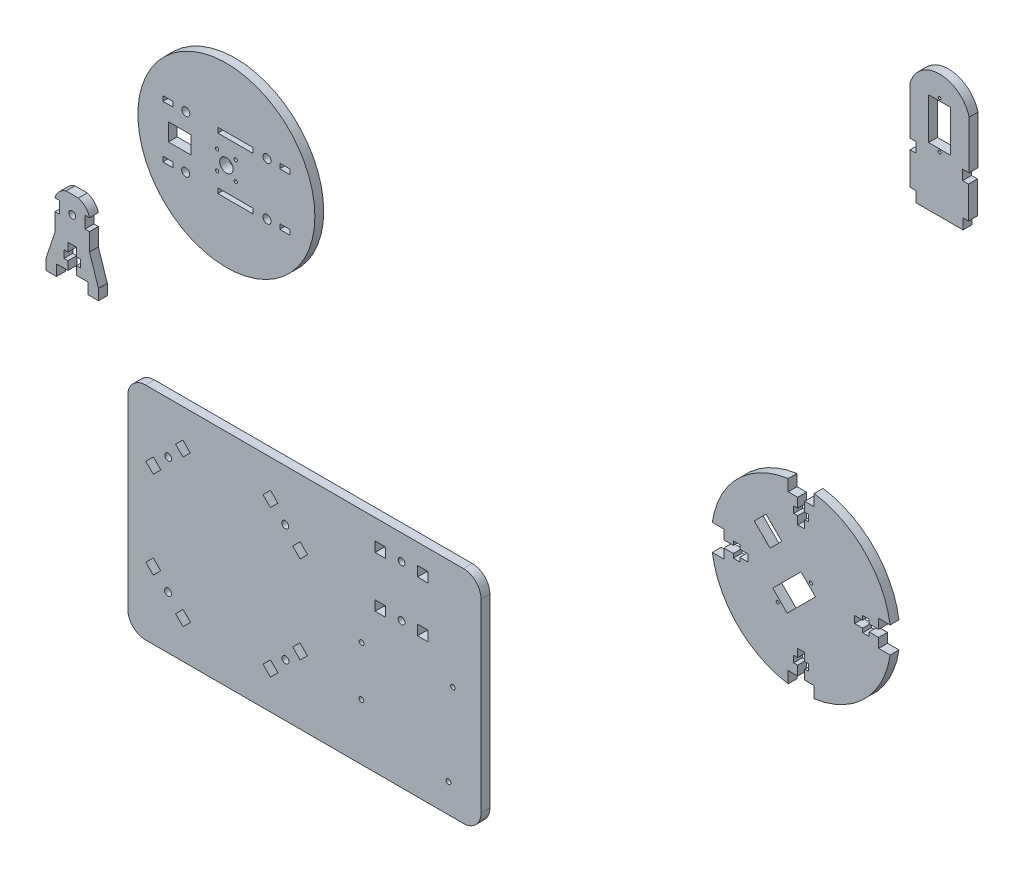
SolidWorks part; units mm, degrees
note: The reader was unsure of these and kept them because the rebuilt part matched: shared geometry of "Sketch2<4>", "Sketch3<3>", "Sketch3<4>".
ref_plane "Front Plane" through (0, 0, 0) normal (0, 0, 1) x (1, 0, 0)
ref_plane "Top Plane" through (0, 0, 0) normal (0, 1, 0) x (1, 0, 0)
ref_plane "Right Plane" through (0, 0, 0) normal (1, 0, 0) x (0, 0, -1)
sketch "Sketch2" plane through (0, 0, 0) normal (0, 0, 1) x (1, 0, 0)
  line L28 (-46.2053, 0) -> (-46.2053, 6.069)
  line L29 (199.603, -121.4578) -> (199.603, -37.9314)
  line L30 (10.2003, -65.1714) -> (14.4333, -69.3774)
  line L31 (189.603, -27.9314) -> (10, -27.9314)
  line L32 (199.603, -37.9314) -> (199.603, -142.6594)
  line L33 (189.603, -152.6594) -> (10, -152.6594)
  line L34 (0, -37.9314) -> (0, -142.6594)
  line L35 (10.2003, -65.1714) -> (14.4337, -60.9108)
  line L36 (14.4333, -69.3774) -> (18.6667, -65.1168)
  line L37 (14.4337, -60.9108) -> (18.6667, -65.1168)
  line L38 (27.0203, -48.3784) -> (31.2263, -52.6114)
  line L39 (27.0203, -48.3784) -> (31.1246, -44.3003)
  line L40 (31.2263, -52.6114) -> (35.3306, -48.5333)
  line L41 (31.1246, -44.3003) -> (35.3306, -48.5333)
  line L42 (76.3823, -48.3784) -> (80.6153, -52.6114)
  line L43 (76.3823, -48.3784) -> (80.6232, -44.1374)
  line L44 (80.6153, -52.6114) -> (84.8562, -48.3704)
  line L45 (80.6232, -44.1374) -> (84.8562, -48.3704)
  line L46 (93.1733, -65.1714) -> (97.4063, -69.3774)
  line L47 (93.1733, -65.1714) -> (97.3783, -60.9393)
  line L48 (97.4063, -69.3774) -> (101.6113, -65.1453)
  line L49 (97.3783, -60.9393) -> (101.6113, -65.1453)
  line L50 (163.7283, -44.9924) -> (169.6553, -44.9924)
  line L51 (163.7283, -44.9924) -> (163.7283, -39.3468)
  line L52 (169.6553, -44.9924) -> (169.6553, -39.3468)
  line L53 (163.7283, -39.3468) -> (169.6553, -39.3468)
  line L54 (139.7403, -44.9924) -> (145.6673, -44.9924)
  line L55 (139.7403, -44.9924) -> (139.7403, -39.3781)
  line L56 (145.6673, -44.9924) -> (145.6673, -39.3781)
  line L57 (139.7403, -39.3781) -> (145.6673, -39.3781)
  line L58 (163.7283, -73.7784) -> (169.6553, -73.7784)
  line L59 (163.7283, -73.7784) -> (163.7283, -68.0524)
  line L60 (169.6553, -73.7784) -> (169.6553, -68.0524)
  line L61 (163.7283, -68.0524) -> (169.6553, -68.0524)
  line L62 (139.7403, -73.7784) -> (145.6673, -73.7784)
  line L63 (139.7403, -73.7784) -> (139.7403, -68.1856)
  line L64 (145.6673, -73.7784) -> (145.6673, -68.1856)
  line L65 (139.7403, -68.1856) -> (145.6673, -68.1856)
  line L66 (10.2003, -114.5602) -> (14.4333, -118.7663)
  line L67 (10.2003, -114.5602) -> (14.406, -110.3275)
  line L68 (14.4333, -118.7663) -> (18.639, -114.5336)
  line L69 (14.406, -110.3275) -> (18.639, -114.5336)
  line L70 (26.9933, -131.3532) -> (31.2263, -135.5866)
  line L71 (26.9933, -131.3532) -> (31.2249, -127.122)
  line L72 (31.2263, -135.5866) -> (35.4579, -131.3554)
  line L73 (31.2249, -127.122) -> (35.4579, -131.3554)
  line L74 (76.3823, -131.3532) -> (80.6153, -135.5866)
  line L75 (76.3823, -131.3532) -> (80.6148, -127.1211)
  line L76 (80.6153, -135.5866) -> (84.8478, -131.3545)
  line L77 (80.6148, -127.1211) -> (84.8478, -131.3545)
  line L78 (93.1733, -114.5602) -> (97.4063, -118.7936)
  line L79 (93.1733, -114.5602) -> (97.2631, -110.4707)
  line L80 (97.4063, -118.7936) -> (101.4961, -114.7041)
  line L81 (97.2631, -110.4707) -> (101.4961, -114.7041)
  line L82 (-46.2053, 6.069) -> (-41.1253, 21.309)
  line L83 (-41.1253, 21.309) -> (-41.1253, 31.309)
  line L84 (-41.1253, 31.309) -> (-38.5853, 31.309)
  line L85 (-38.5853, 31.309) -> (-38.5853, 38.082)
  line L86 (-38.5853, 38.082) -> (-41.1253, 38.082)
  line L87 (-46.2053, 0) -> (-40.2783, 0)
  line L88 (-40.2783, 0) -> (-40.2783, 6.209)
  line L89 (-40.2783, 6.209) -> (-33.7883, 6.209)
  line L90 (-33.7883, 6.209) -> (-33.7883, 11.008)
  line L91 (-33.7883, 11.008) -> (-36.0453, 11.008)
  line L92 (-36.0453, 11.008) -> (-36.0453, 15.241)
  line L93 (-36.0453, 15.241) -> (-33.7873, 15.241)
  line L94 (-33.7873, 15.241) -> (-33.7873, 20.019)
  line L95 (-33.7873, 20.019) -> (-28.9633, 20.019)
  line L96 (-31.3753, 20.019) -> (-31.3753, 15.222)
  line L110 (-34.8506, 44.6171) -> (-31.3662, 44.6171)
  line L111 (-31.3753, 34.659) -> (-31.3753, -6.6875) construction
  line L112 (0, 0) -> (-40.2783, 0) construction
  line L113 (-16.5453, 0) -> (-22.4723, 0)
  line L114 (-27.9001, 44.6171) -> (-31.3845, 44.6171)
  line L115 (-28.9633, 15.241) -> (-28.9633, 20.019)
  line L116 (-26.7053, 15.241) -> (-28.9633, 15.241)
  line L117 (-26.7053, 11.008) -> (-26.7053, 15.241)
  line L118 (-28.9623, 11.008) -> (-26.7053, 11.008)
  line L119 (-28.9623, 6.209) -> (-28.9623, 11.008)
  line L120 (-22.4723, 6.209) -> (-28.9623, 6.209)
  line L121 (-22.4723, 0) -> (-22.4723, 6.209)
  line L122 (-24.1653, 38.082) -> (-21.6253, 38.082)
  line L123 (-24.1653, 31.309) -> (-24.1653, 38.082)
  line L124 (-21.6253, 31.309) -> (-24.1653, 31.309)
  line L125 (-21.6253, 21.309) -> (-21.6253, 31.309)
  line L126 (-16.5453, 6.069) -> (-21.6253, 21.309)
  line L127 (-16.5453, 0) -> (-16.5453, 6.069)
  line L128 (22.8394, -56.7305) -> (106.4635, -140.1948) construction
  line L129 (22.7571, -122.886) -> (88.9638, -56.7949) construction
  line L130 (22.7571, -122.886) -> (38.9461, -139.075) construction
  line L131 (22.7571, -122.886) -> (3.8152, -103.9442) construction
  line L132 (0, 0) -> (0, -90.2954) construction
  arc A0 (199.603, -37.9314) -> (189.603, -27.9314) centre (189.603, -37.9314) ccw
  arc A1 (189.603, -152.6594) -> (199.603, -142.6594) centre (189.603, -142.6594) ccw
  arc A2 (10, -152.6594) -> (0, -142.6594) centre (10, -142.6594) cw
  arc A3 (10, -27.9314) -> (0, -37.9314) centre (10, -37.9314) ccw
  arc A4 (199.603, -37.9314) -> (189.603, -27.9314) centre (189.603, -37.9314) ccw
  circle A5 centre (22.8394, -56.7305) radius 1.9277
  circle A6 centre (88.9638, -56.7949) radius 1.9654
  circle A7 centre (154.6946, -42.0768) radius 1.8926
  circle A8 centre (154.6904, -70.942) radius 1.9315
  circle A9 centre (132.0883, -92.915) radius 1.329
  circle A10 centre (183.6758, -88.8865) radius 1.2561
  circle A11 centre (22.7571, -122.886) radius 1.955
  circle A12 centre (89.0892, -122.8537) radius 1.9478
  circle A13 centre (132.0182, -120.8684) radius 1.3462
  circle A14 centre (181.2213, -136.408) radius 1.3886
  circle A17 centre (-31.3753, 34.659) radius 1.955
  arc A19 (-34.8506, 44.6171) -> (-41.1253, 38.082) centre (-32.2253, 35.8165) ccw
  arc A20 (-27.9001, 44.6171) -> (-21.6253, 38.082) centre (-30.5254, 35.8165) cw
  point P2 (33.3421, -133.471)
  dimension "D1" = 10
  dimension "D2" = 10
  dimension "D3" = 6.49
  dimension "D15" = 3.91
  dimension "D16" = 14.64
  dimension "D18" = 3.91
  dimension "D19" = 5.984
  dimension "D4" = 5.927
  dimension "D5" = 2.54
  dimension "D6" = 7.338
  dimension "D7" = 6.773
  dimension "D8" = 10
  dimension "D9" = 15.24
  dimension "D10" = 6.069
  dimension "D11" = 40.2783
  dimension "D12" = 5.08
  dimension "D13" = 34.659
  dimension "D14" = 9.9582
  dimension "D17" = 9.75
  dimension "D20" = 46.8819
extrude "Boss-Extrude3" add sketch "Sketch2" along normal blind 5 contours L31 A3 L34 A2 L33 A1 L32 L29 A0 A14 A13 A12 A11 A10 A9 A8 A7 A6 A5 L79 L81 L80 L78 L75 L77 L76 L74 L71 L73 L72 L70 L67 L69 L68 L66 L63
extrude "Boss-Extrude4" add sketch "Sketch2<4>" along normal blind 5 separate body
sketch "Sketch2<4>" plane through (0, 0, 0) normal (0, 0, 1) x (1, 0, 0) same geometry as "Sketch2"
sketch "Sketch3" plane through (0, 0, 5) normal (0, 0, 1) x (1, 0, 0)
  line L0 (24.835, 123.613) -> (30.4795, 123.613)
  line L1 (24.835, 123.613) -> (24.835, 120.7918)
  line L2 (30.4795, 123.613) -> (30.4795, 120.7918)
  line L3 (24.835, 120.7918) -> (30.4795, 120.7918)
  line L4 (27.9395, 102.4605) -> (40.6396, 102.4605)
  line L5 (27.9395, 102.4605) -> (27.9395, 112.3605)
  line L6 (40.6396, 102.4605) -> (40.6396, 112.3605)
  line L7 (27.9395, 112.3605) -> (40.6396, 112.3605)
  line L8 (24.835, 91.1572) -> (30.4795, 91.1572)
  line L9 (24.835, 91.1572) -> (24.835, 94.0005)
  line L10 (30.4795, 91.1572) -> (30.4795, 94.0005)
  line L11 (24.835, 94.0005) -> (30.4795, 94.0005)
  line L12 (55.8789, 91.1572) -> (55.8789, 93.9795)
  line L13 (55.8789, 91.1572) -> (75.6506, 91.1572)
  line L14 (55.8789, 93.9795) -> (75.6506, 93.9795)
  line L15 (75.6506, 91.1572) -> (75.6506, 93.9795)
  line L16 (55.8789, 120.79) -> (75.6348, 120.79)
  line L17 (55.8789, 120.79) -> (55.8789, 123.646)
  line L18 (75.6348, 120.79) -> (75.6348, 123.646)
  line L19 (55.8789, 123.646) -> (75.6348, 123.646)
  line L20 (90.876, 120.79) -> (96.5205, 120.79)
  line L21 (90.876, 120.79) -> (90.876, 123.5848)
  line L22 (96.5205, 120.79) -> (96.5205, 123.5848)
  line L23 (90.876, 123.5848) -> (96.5205, 123.5848)
  line L24 (90.876, 91.1572) -> (96.5205, 91.1572)
  line L25 (90.876, 91.1572) -> (90.876, 93.9768)
  line L26 (96.5205, 91.1572) -> (96.5205, 93.9768)
  line L27 (90.876, 93.9768) -> (96.5205, 93.9768)
  line L28 (378.178, 12.418) -> (378.178, 18.9092)
  line L29 (378.178, 18.9092) -> (383.54, 18.9092)
  line L30 (383.54, 18.9092) -> (383.54, 24.2715)
  line L31 (383.54, 24.2715) -> (381.282, 24.2715)
  line L32 (381.282, 24.2715) -> (381.282, 27.9395)
  line L33 (381.282, 27.9395) -> (383.54, 27.9395)
  line L34 (383.54, 27.9395) -> (383.54, 32.4561)
  line L35 (383.54, 32.4561) -> (387.491, 32.4561)
  line L36 (387.491, 32.4561) -> (387.491, 27.9395)
  line L37 (387.491, 27.9395) -> (389.749, 27.9395)
  line L38 (389.749, 27.9395) -> (389.749, 24.2715)
  line L39 (389.749, 24.2715) -> (387.491, 24.2715)
  line L40 (387.491, 24.2715) -> (387.491, 18.9092)
  line L41 (387.491, 18.9092) -> (392.853, 18.9092)
  line L42 (392.853, 18.9092) -> (392.853, 12.418)
  line L43 (435.751, 55.3154) -> (429.26, 55.3154)
  line L44 (429.26, 55.3154) -> (429.26, 60.6777)
  line L45 (429.26, 60.6777) -> (423.898, 60.6777)
  line L46 (423.898, 60.6777) -> (423.898, 58.4209)
  line L47 (423.898, 58.4209) -> (420.229, 58.4209)
  line L48 (420.229, 58.4209) -> (420.229, 60.6777)
  line L49 (420.229, 60.6777) -> (415.713, 60.6777)
  line L50 (415.713, 60.6777) -> (415.713, 64.6289)
  line L51 (415.713, 64.6289) -> (420.229, 64.6289)
  line L52 (420.229, 64.6289) -> (420.229, 66.8877)
  line L53 (420.229, 66.8877) -> (423.898, 66.8877)
  line L54 (423.898, 66.8877) -> (423.898, 64.6289)
  line L55 (423.898, 64.6289) -> (429.26, 64.6289)
  line L56 (429.26, 64.6289) -> (429.26, 69.9902)
  line L57 (429.26, 69.9902) -> (435.751, 69.9902)
  line L58 (392.853, 112.889) -> (392.853, 106.398)
  line L59 (392.853, 106.398) -> (387.491, 106.398)
  line L60 (387.491, 106.398) -> (387.491, 101.035)
  line L61 (387.491, 101.035) -> (389.749, 101.035)
  line L62 (389.749, 101.035) -> (389.749, 97.3672)
  line L63 (389.749, 97.3672) -> (387.491, 97.3672)
  line L64 (387.491, 97.3672) -> (387.491, 92.8506)
  line L65 (387.491, 92.8506) -> (383.54, 92.8506)
  line L66 (383.54, 92.8506) -> (383.54, 97.3672)
  line L67 (383.54, 97.3672) -> (381.282, 97.3672)
  line L68 (381.282, 97.3672) -> (381.282, 101.035)
  line L69 (381.282, 101.035) -> (383.54, 101.035)
  line L70 (383.54, 101.035) -> (383.54, 106.398)
  line L71 (383.54, 106.398) -> (378.178, 106.398)
  line L72 (378.178, 106.398) -> (378.178, 112.889)
  line L73 (335.279, 55.3154) -> (341.771, 55.3154)
  line L74 (341.771, 55.3154) -> (341.771, 60.6777)
  line L75 (341.771, 60.6777) -> (347.133, 60.6777)
  line L76 (347.133, 60.6777) -> (347.133, 58.4209)
  line L77 (347.133, 58.4209) -> (350.802, 58.4209)
  line L78 (350.802, 58.4209) -> (350.802, 60.6777)
  line L79 (350.802, 60.6777) -> (355.318, 60.6777)
  line L80 (355.318, 60.6777) -> (355.318, 64.6289)
  line L81 (355.318, 64.6289) -> (350.802, 64.6289)
  line L82 (350.802, 64.6289) -> (350.802, 66.8877)
  line L83 (350.802, 66.8877) -> (347.133, 66.8877)
  line L84 (347.133, 66.8877) -> (347.133, 64.6289)
  line L85 (347.133, 64.6289) -> (341.771, 64.6289)
  line L86 (341.771, 64.6289) -> (341.771, 69.9902)
  line L87 (341.771, 69.9902) -> (335.279, 69.9902)
  line L88 (369.429, 54.8926) -> (385.374, 70.8379)
  line L89 (369.429, 54.8926) -> (377.6042, 46.7175)
  line L90 (385.374, 70.8379) -> (393.5492, 62.6628)
  line L91 (377.6042, 46.7175) -> (393.5492, 62.6628)
  line L92 (358.987, 82.5498) -> (365.619, 89.1826)
  line L93 (358.987, 82.5498) -> (367.8931, 73.6448)
  line L94 (365.619, 89.1826) -> (374.5251, 80.2776)
  line L95 (367.8931, 73.6448) -> (374.5251, 80.2776)
  line L96 (450.427, 283.916) -> (450.427, 289.843)
  line L97 (450.427, 289.843) -> (447.04, 289.843)
  line L98 (447.04, 289.843) -> (447.04, 308.187)
  line L99 (447.04, 308.187) -> (450.427, 308.187)
  line L100 (450.427, 308.187) -> (450.427, 313.832)
  line L101 (450.427, 313.832) -> (447.012, 313.832)
  line L102 (447.012, 313.832) -> (447.012, 340.8024)
  line L104 (450.427, 283.916) -> (476.956, 283.916)
  line L105 (476.956, 283.916) -> (476.956, 289.843)
  line L106 (476.956, 289.843) -> (480.0727, 289.843)
  line L107 (480.0727, 289.843) -> (480.0727, 307.9082)
  line L108 (480.0727, 307.9082) -> (476.6867, 307.9082)
  line L109 (476.6867, 307.9082) -> (476.6867, 313.5532)
  line L110 (476.6867, 313.5532) -> (480.399, 313.5532)
  line L111 (480.399, 313.5532) -> (480.399, 340.8024)
  line L112 (457.482, 340.36) -> (469.9, 340.36)
  line L113 (469.9, 340.36) -> (469.9, 316.935)
  line L114 (469.9, 316.935) -> (457.482, 316.935)
  line L115 (457.482, 316.935) -> (457.482, 340.36)
  line L116 (55.4954, -43.6841) -> (65.8504, -43.6841)
  line L117 (75.8504, -65.9541) -> (75.8504, -53.6841)
  line L118 (75.8504, -65.9541) -> (82.0584, -65.9541)
  line L119 (82.0584, -65.9541) -> (82.0584, -72.1631)
  line L120 (82.0584, -72.1631) -> (75.8504, -72.1631)
  line L121 (75.8504, -72.1631) -> (75.8504, -76.9601)
  line L122 (75.8504, -76.9601) -> (70.4864, -76.9601)
  line L123 (70.4864, -76.9601) -> (70.4864, -74.7031)
  line L124 (70.4864, -74.7031) -> (66.8184, -74.7031)
  line L125 (66.8184, -74.7031) -> (66.8184, -76.9601)
  line L126 (66.8184, -76.9601) -> (62.0204, -76.9601)
  line L127 (62.0204, -76.9601) -> (62.0204, -81.1941)
  line L128 (62.0204, -81.1941) -> (66.8184, -81.1941)
  line L129 (66.8184, -81.1941) -> (66.8184, -83.4511)
  line L130 (66.8184, -83.4511) -> (70.4864, -83.4511)
  line L131 (70.4864, -83.4511) -> (70.4864, -81.1941)
  line L132 (70.4864, -81.1941) -> (75.8504, -81.1941)
  line L133 (75.8504, -81.1941) -> (75.8504, -96.9971)
  line L134 (75.8504, -96.9971) -> (82.0584, -96.9971)
  line L135 (82.0584, -96.9971) -> (82.0584, -117.3181)
  line L136 (82.0584, -117.3181) -> (75.8504, -117.3181)
  line L137 (75.8504, -117.3181) -> (75.8504, -122.9631)
  line L138 (75.8504, -122.9631) -> (70.4864, -122.9631)
  line L139 (70.4864, -122.9631) -> (70.4864, -120.7051)
  line L140 (70.4864, -120.7051) -> (66.8184, -120.7051)
  line L141 (66.8184, -120.7051) -> (66.8184, -122.9631)
  line L142 (66.8184, -122.9631) -> (62.0204, -122.9631)
  line L143 (62.0204, -122.9631) -> (62.0204, -127.1961)
  line L144 (62.0204, -127.1961) -> (66.8184, -127.1961)
  line L145 (66.8184, -127.1961) -> (66.8184, -129.4531)
  line L146 (66.8184, -129.4531) -> (70.4864, -129.4531)
  line L147 (70.4864, -129.4531) -> (70.4864, -127.1961)
  line L148 (70.4864, -127.1961) -> (75.8504, -127.1961)
  line L149 (75.8504, -127.1961) -> (75.8504, -131.9941)
  line L150 (75.8504, -131.9941) -> (82.0584, -131.9941)
  line L151 (82.0584, -131.9941) -> (82.0584, -138.2021)
  line L152 (82.0584, -138.2021) -> (75.8504, -138.2021)
  line L153 (75.8504, -138.2021) -> (75.8504, -150.4734)
  line L154 (55.4954, -160.4734) -> (65.8504, -160.4734)
  line L156 (45.4954, -146.8124) -> (45.4954, -150.4734)
  line L157 (45.4954, -146.8124) -> (45.4954, -53.6841)
  line L158 (51.5398, -110.4734) -> (69.8838, -110.4734)
  line L159 (51.5398, -110.4734) -> (51.5398, -103.8419)
  line L160 (69.8838, -110.4734) -> (69.8838, -103.8419)
  line L161 (51.5398, -103.8419) -> (69.8838, -103.8419)
  line L162 (60.7118, 107.4105) -> (60.7118, 0) construction
  line L163 (60.7118, 0) -> (0, 0) construction
  line L164 (60.7118, -103.8419) -> (60.7118, -201.5509) construction
  line L165 (60.7118, -201.5509) -> (60.7118, 0) construction
  line L166 (82.0584, -107.1576) -> (60.7118, -107.1576) construction
  line L167 (60.7118, 107.4105) -> (10.7118, 107.4105)
  circle A0 centre (60.7118, 107.4105) radius 50
  circle A1 centre (60.7118, 107.4105) radius 3.785
  circle A5 centre (65.9618, 102.0605) radius 0.925
  circle A6 centre (37.788, 122.202) radius 2.272
  circle A7 centre (37.6751, 92.5784) radius 2.2712
  circle A8 centre (83.6793, 122.211) radius 2.2714
  circle A9 centre (83.6859, 92.5714) radius 2.2773
  circle A10 centre (372.1966, 49.3897) radius 0.8351
  circle A11 centre (391.0345, 68.2035) radius 0.9211
  arc A13 (435.751, 69.9902) -> (392.853, 112.889) centre (385.5154, 62.6535) ccw
  arc A14 (480.399, 340.8024) -> (447.012, 340.8024) centre (463.7055, 336.3181) ccw
  circle A15 centre (463.6401, 315.3484) radius 0.8619
  circle A16 centre (463.657, 341.8058) radius 0.7486
  arc A17 (335.28, 55.3154) -> (378.178, 12.418) centre (385.5154, 62.6535) ccw
  arc A18 (392.853, 12.418) -> (435.7508, 55.3154) centre (385.5154, 62.6535) ccw
  arc A19 (378.178, 112.889) -> (335.2798, 69.9902) centre (385.5154, 62.6535) ccw
  arc A20 (75.8504, -150.4734) -> (65.8504, -160.4734) centre (65.8504, -150.4734) cw
  arc A21 (55.4954, -160.4734) -> (45.4954, -150.4734) centre (55.4954, -150.4734) cw
  arc A22 (75.8504, -53.6841) -> (65.8504, -43.6841) centre (65.8504, -53.6841) ccw
  arc A23 (45.4954, -53.6841) -> (55.4954, -43.6841) centre (55.4954, -53.6841) cw
  circle A24 centre (55.4618, 102.0605) radius 0.925
  circle A25 centre (65.9618, 112.7605) radius 0.925
  circle A26 centre (55.4618, 112.7605) radius 0.925
  point P6 (40.6396, 107.4105)
  point P10 (69.8838, -107.1576)
  dimension "D1" = 10
  dimension "D2" = 18.0652
  dimension "D17" = 100
  dimension "D19" = 1.85
  dimension "D21" = 7.57
  dimension "D3" = 18.344
  dimension "D4" = 36.563
  dimension "D5" = 107.1576
  dimension "D6" = 20.321
  dimension "D7" = 60.7118
  dimension "D8" = 0
  dimension "D9" = 6.6315
  dimension "D10" = 14.676
  dimension "D11" = 6.208
  dimension "D12" = 6.208
  dimension "D13" = 50
  dimension "D14" = 6.208
  dimension "D15" = 22.27
  dimension "D16" = 37.8878
  dimension "D18" = 107.4105
  dimension "D20" = 5.25
  dimension "D22" = 5.35
  dimension "D23" = 9.9
  dimension "D24" = 12.7001
  dimension "D25" = 20.0722
extrude "Boss-Extrude5" add sketch "Sketch3" along normal blind 5 separate body contours L72 A19 L87 L86 L85 L84 L83 L82 L81 L80 L79 L78 L77 L76 L75 L74 L73 A17 L28 L29 L30 L31 L32 L33 L34 L35 L36 L37 L38 L39 L40 L41 L42 A18 L43 L44 L45 L46 L47 L48 L49 L50 L51 L52 L53 L54 L55 L56 L57 A13 L58
extrude "Boss-Extrude6" add sketch "Sketch3<3>" along normal blind 5 separate body contours L111 A14 L102 L101 L100 L99 L98 L97 L96 L104 L105 L106 L107 L108 L109 L110 A16 A15 L114 L115 L112 L113
sketch "Sketch3<3>" plane through (0, 0, 5) normal (0, 0, 1) x (1, 0, 0) same geometry as "Sketch3"
extrude "Boss-Extrude7" add sketch "Sketch3<4>" along normal blind 5 separate body
sketch "Sketch3<4>" plane through (0, 0, 5) normal (0, 0, 1) x (1, 0, 0) same geometry as "Sketch3"
